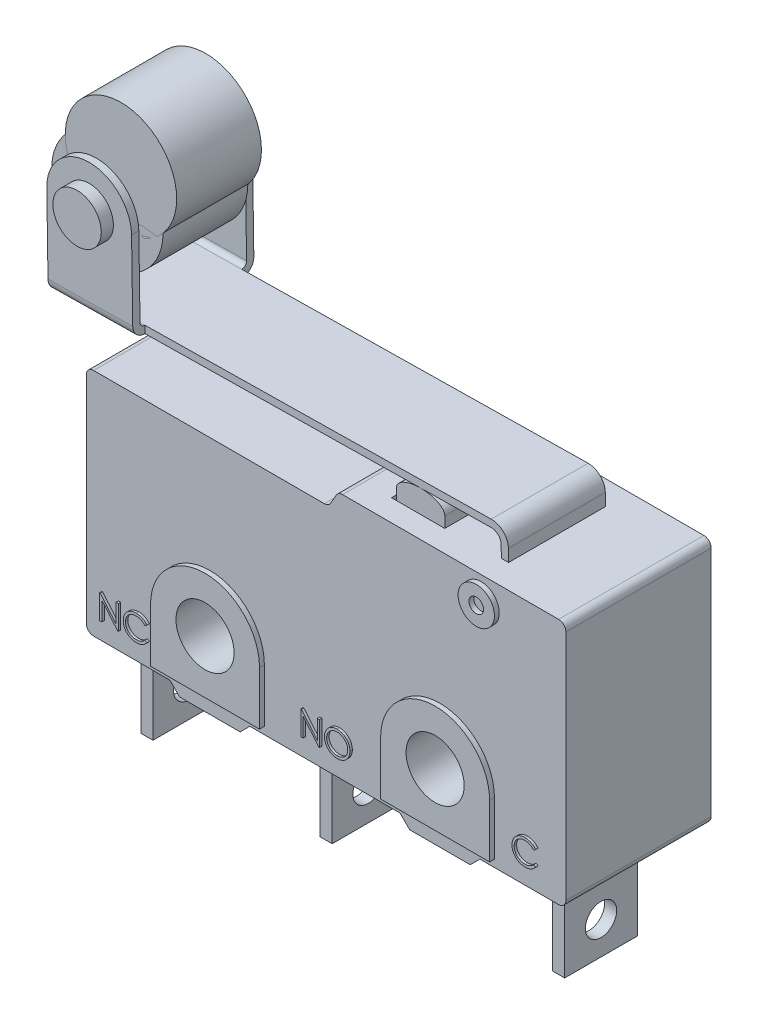
SolidWorks part; units mm, degrees
other "Marcação1"
sketch "Esboço1" plane through (6.45, -3.6, 3.2) normal (0.2977, -0.0394, 0.9539) x (0.9446, 0.157, -0.2883)
ref_plane "Plan de face" through (0, 0, 0) normal (0, 0, 1) x (1, 0, 0)
ref_plane "Plan de dessus" through (0, 0, 0) normal (0, 1, 0) x (1, 0, 0)
ref_plane "Plan de droite" through (0, 0, 0) normal (1, 0, 0) x (0, 0, -1)
sketch "Esquisse1" plane through (0, 0, 0) normal (0, 0, 1) x (1, 0, 0)
  line L0 (-7, 0) -> (-9.5, 0)
  line L1 (-9.5, 0) -> (-9.9, 0.4)
  line L2 (-9.9, 0.4) -> (-13.05, 0.4)
  line L3 (-13.35, 0.7) -> (-13.35, 9.6)
  line L4 (-13.05, 9.9) -> (-3.5232, 9.9)
  line L5 (-3.2634, 10.05) -> (-3.0325, 10.45)
  line L6 (-2.7726, 10.6) -> (6.15, 10.6)
  line L7 (6.45, 10.3) -> (6.45, 0.7)
  line L8 (6.15, 0.4) -> (2.9, 0.4)
  line L9 (2.9, 0.4) -> (2.5, 0)
  line L10 (2.5, 0) -> (0, 0)
  line L11 (0, 0) -> (-0.4, 0.4)
  line L12 (-0.4, 0.4) -> (-6.6, 0.4)
  line L13 (-6.6, 0.4) -> (-7, 0)
  line L14 (-8.25, 2.9) -> (-8.25, 0) construction
  line L15 (1.25, 2.9) -> (1.25, 0) construction
  circle A0 centre (-8.25, 2.9) radius 1.2
  circle A1 centre (1.25, 2.9) radius 1.2
  arc A2 (-3.5232, 9.9) -> (-3.2634, 10.05) centre (-3.5232, 10.2) ccw
  arc A3 (-3.0325, 10.45) -> (-2.7726, 10.6) centre (-2.7726, 10.3) cw
  arc A4 (-13.05, 0.4) -> (-13.35, 0.7) centre (-13.05, 0.7) cw
  arc A5 (-13.35, 9.6) -> (-13.05, 9.9) centre (-13.05, 9.6) cw
  arc A6 (6.45, 0.7) -> (6.15, 0.4) centre (6.15, 0.7) cw
  arc A7 (6.15, 10.6) -> (6.45, 10.3) centre (6.15, 10.3) cw
  point P23 (-3.35, 9.9)
  point P30 (-13.35, 9.9)
  dimension "D2" = 9.5
  dimension "D3" = 2.4
  dimension "D4" = 2.9
  dimension "D11" = 0.3
  dimension "D1" = 2.5
  dimension "D5" = 5.1
  dimension "D6" = 19.8
  dimension "D7" = 10
  dimension "D8" = 0.7
  dimension "D9" = 10.6
  dimension "D10" = 0.4
  dimension "D12" = 120
  dimension "D13" = 135
extrude "Boss.-Extru.1" add sketch "Esquisse1" along normal mid plane 6
sketch "Esquisse2" plane through (0, 0, 0) normal (0, 0, 1) x (1, 0, 0)
  line L0 (-10.5, 0.7) -> (-6, 0.7)
  line L1 (-6, 0.7) -> (-6, 2.9)
  line L2 (-10.5, 2.9) -> (-10.5, 0.7)
  line L3 (-1, 2.9) -> (-1, 0.7)
  line L4 (-1, 0.7) -> (3.5, 0.7)
  line L5 (3.5, 0.7) -> (3.5, 2.9)
  line L6 (6.45, 0.7) -> (6.45, 10.3) construction
  line L7 (6.15, 10.6) -> (-2.7726, 10.6) construction
  arc A0 (-6, 2.9) -> (-10.5, 2.9) centre (-8.25, 2.9) ccw
  circle A1 centre (-8.25, 2.9) radius 1.2 construction
  circle A2 centre (-8.25, 2.9) radius 1.2
  arc A3 (3.5, 2.9) -> (-1, 2.9) centre (1.25, 2.9) ccw
  circle A4 centre (1.25, 2.9) radius 1.2
  circle A5 centre (2.95, 9.6) radius 0.75
  circle A6 centre (2.95, 9.6) radius 0.3
  dimension "D1" = 2.25
  dimension "D5" = 3.5
  dimension "D7" = 1.5
  dimension "D8" = 0.6
  dimension "D2" = 2.2
  dimension "D4" = 5
  dimension "D6" = 1
  dimension "D3" = 2
extrude "Boss.-Extru.2" add sketch "Esquisse2" along normal mid plane 6.4
sketch "Esquisse3" plane through (0, 0, -3) normal (0, 0, -1) x (-1, 0, 0)
  text T0 "5A 125-250V~ 10T85" font "Century Gothic" height 1
extrude "Boss.-Extru.3" add sketch "Esquisse3" along normal blind 0.1
sketch "Esquisse18" plane through (0, 0, 0) normal (0, 0, 1) x (1, 0, 0)
  line L0 (6.15, 10.6) -> (-2.7726, 10.6) construction
  line L1 (-1.65, 10.6) -> (0.55, 10.6)
  line L2 (-1.65, 10.6) -> (-1.65, 8.6)
  line L3 (-1.65, 8.6) -> (0.55, 8.6)
  line L4 (0.55, 10.6) -> (0.55, 8.6)
  line L5 (6.45, 0.7) -> (6.45, 10.3) construction
  dimension "D1" = 5.9
  dimension "D2" = 2
  dimension "D3" = 2.2
extrude "Enlèv. mat.-Extru.3" cut sketch "Esquisse18" against normal mid plane 4.2
sketch "Esquisse9" plane through (0, 0, 0) normal (0, 0, 1) x (1, 0, 0)
  line L0 (2.785, 10.6) -> (2.7775, 11.0976)
  line L1 (6.15, 10.6) -> (-2.7726, 10.6) construction
  line L2 (2.3715, 11.4915) -> (-15.4265, 11.2241)
  line L3 (-15.4265, 11.2241) -> (-15.431, 11.5241)
  line L4 (-9.5, 0) -> (-7, 0) construction
  line L5 (-15.431, 11.5241) -> (2.367, 11.7915)
  line L6 (3.0775, 11.1021) -> (3.085, 10.6)
  line L7 (3.085, 10.6) -> (2.785, 10.6)
  line L8 (2.95, 9.6) -> (2.935, 10.6) construction
  arc A1 (2.7775, 11.0976) -> (2.3715, 11.4915) centre (2.3775, 11.0916) ccw
  arc A2 (2.367, 11.7915) -> (3.0775, 11.1021) centre (2.3775, 11.0916) cw
  circle A3 centre (-13.733, 15) radius 2.3 construction
  dimension "D4" = 0.4
  dimension "D5" = 0.7
  dimension "D9" = 4.6
  dimension "D1" = 0.3
  dimension "D2" = 0.3
  dimension "D3" = 2.2
  dimension "D6" = 18.5
  dimension "D7" = 1.75
  dimension "D10" = 3.75
  dimension "D11" = 15
extrude "Boss.-Extru.15" add sketch "Esquisse9" along normal mid plane 4
sketch "Esquisse10" plane through (0, 0, 0) normal (0, 0, 1) x (1, 0, 0)
  line L0 (-15.4265, 11.2241) -> (-15.4828, 14.9737)
  line L1 (-11.9832, 15.0263) -> (-11.9269, 11.2767)
  line L2 (-15.4265, 11.2241) -> (2.3715, 11.4915) construction
  line L3 (-11.9269, 11.2767) -> (-15.4265, 11.2241)
  arc A0 (-15.4828, 14.9737) -> (-11.9832, 15.0263) centre (-13.733, 15) cw
extrude "Boss.-Extru.16" add sketch "Esquisse10" along normal mid plane 5
sketch "Esquisse5" plane through (0, 0, 0) normal (0, 0, 1) x (1, 0, 0)
  line L0 (-1.55, 10.9474) -> (-1.55, 9.4474)
  line L2 (-1.55, 9.4474) -> (0.45, 9.4474)
  line L3 (0.45, 9.4474) -> (0.45, 10.9474)
  line L5 (-1.55, 10.9474) -> (0.45, 10.9474) construction
  line L6 (6.45, 0.7) -> (6.45, 10.3) construction
  line L7 (-11.9269, 11.2767) -> (2.3715, 11.4915) construction
  ellipse E0 centre (-0.55, 10.9474) end of major axis (0.45, 10.9474) minor radius 0.5 (0.45, 10.9474) -> (-1.55, 10.9474) ccw
  dimension "D1" = 0.5
  dimension "D2" = 2
  dimension "D4" = 2
  dimension "D5" = 6
extrude "Boss.-Extru.4" add sketch "Esquisse5" along normal mid plane 4 separate body
sketch "Esquisse11" plane through (0, 0, 0) normal (0, 0, 1) x (1, 0, 0)
  line L0 (-11.9314, 11.5767) -> (-15.431, 11.5241)
  line L2 (-15.431, 11.5241) -> (-15.5211, 17.5241)
  line L3 (-15.5211, 17.5241) -> (-12.0215, 17.5767)
  line L4 (-12.0215, 17.5767) -> (-11.9314, 11.5767)
  dimension "D1" = 6
extrude "Enlèv. mat.-Extru.1" cut sketch "Esquisse11" against normal mid plane 4.4
sketch "Esquisse12" plane through (0, 0, 0) normal (0, 0, 1) x (1, 0, 0)
  circle A0 centre (-13.733, 15) radius 1
  dimension "D1" = 2
extrude "Boss.-Extru.17" add sketch "Esquisse12" along normal mid plane 6
sketch "Esquisse13" plane through (0, 0, 0) normal (0, 0, 1) x (1, 0, 0)
  circle A0 centre (-13.733, 15) radius 2.3
  circle A1 centre (-13.733, 15) radius 2.3 construction
extrude "Boss.-Extru.18" add sketch "Esquisse13" along normal mid plane 3.5
fillet "Congé1" radius 0.2 2 edges at (-13.6812, 11.5504, 2.2) (-13.6812, 11.5504, -2.2)
fillet "Congé2" radius 0.5 2 edges at (-13.6767, 11.2504, 2.5) (-13.6767, 11.2504, -2.5)
sketch "Esquisse15" plane through (0, 0, 0) normal (0, 0, 1) x (1, 0, 0)
  line L1 (4.4, 0.5) -> (4.9, 0.5)
  line L2 (4.4, 0.5) -> (4.4, -3.6)
  line L3 (4.4, -3.6) -> (4.9, -3.6)
  line L4 (4.9, 0.5) -> (4.9, -3.6)
  line L5 (-6.6, 0.4) -> (-0.4, 0.4) construction
  line L6 (-5.2, 0.4) -> (-4.7, 0.4)
  line L7 (-5.2, 0.4) -> (-5.2, -3.6)
  line L8 (-5.2, -3.6) -> (-4.7, -3.6)
  line L9 (-4.7, 0.4) -> (-4.7, -3.6)
  line L10 (-13.05, 0.4) -> (-9.9, 0.4) construction
  line L11 (-12.6, 0.4) -> (-12.1, 0.4)
  line L12 (-12.6, 0.4) -> (-12.6, -3.6)
  line L13 (-12.6, -3.6) -> (-12.1, -3.6)
  line L14 (-12.1, 0.4) -> (-12.1, -3.6)
  line L16 (6.45, 0.7) -> (6.45, 10.3) construction
  dimension "D1" = 9.6
  dimension "D2" = 7.4
  dimension "D3" = 0.5
  dimension "D4" = 1.55
  dimension "D5" = 4
extrude "Boss.-Extru.19" add sketch "Esquisse15" along normal mid plane 3 separate body
sketch "Esquisse16" plane through (-12.6, 0, 0) normal (-1, 0, 0) x (0, 0, 1)
  circle A0 centre (0, -2.2572) radius 0.647
extrude "Enlèv. mat.-Extru.2" cut sketch "Esquisse16" against normal through all
sketch "Esquisse7" plane through (0, 0, -3) normal (0, 0, -1) x (-1, 0, 0)
  text T0 "1                 3                  2" font "Century Gothic" height 1
extrude "Boss.-Extru.5" add sketch "Esquisse7" along normal blind 0.1
sketch "Esquisse8" plane through (0, 0, 3) normal (0, 0, 1) x (1, 0, 0)
  text T0 "NC                NO                 C" font "Century Gothic" height 1
extrude "Boss.-Extru.6" add sketch "Esquisse8" along normal blind 0.1
sketch "Esquisse17" plane through (0, 0, 0) normal (0, 0, 1) x (1, 0, 0)
  line L1 (-9.5, 0) -> (-7, 0) construction
  arc A0 (-13.733, 15) -> (-13.1706, 16.5) centre (2.95, 9.6) cw construction
  circle A1 centre (-13.1706, 16.5) radius 2.3
  circle A2 centre (-13.733, 15) radius 2.3 construction
  dimension "D1" = 16.5
extrude "Boss.-Extru.20" add sketch "Esquisse17" along normal mid plane 3.5 separate body
